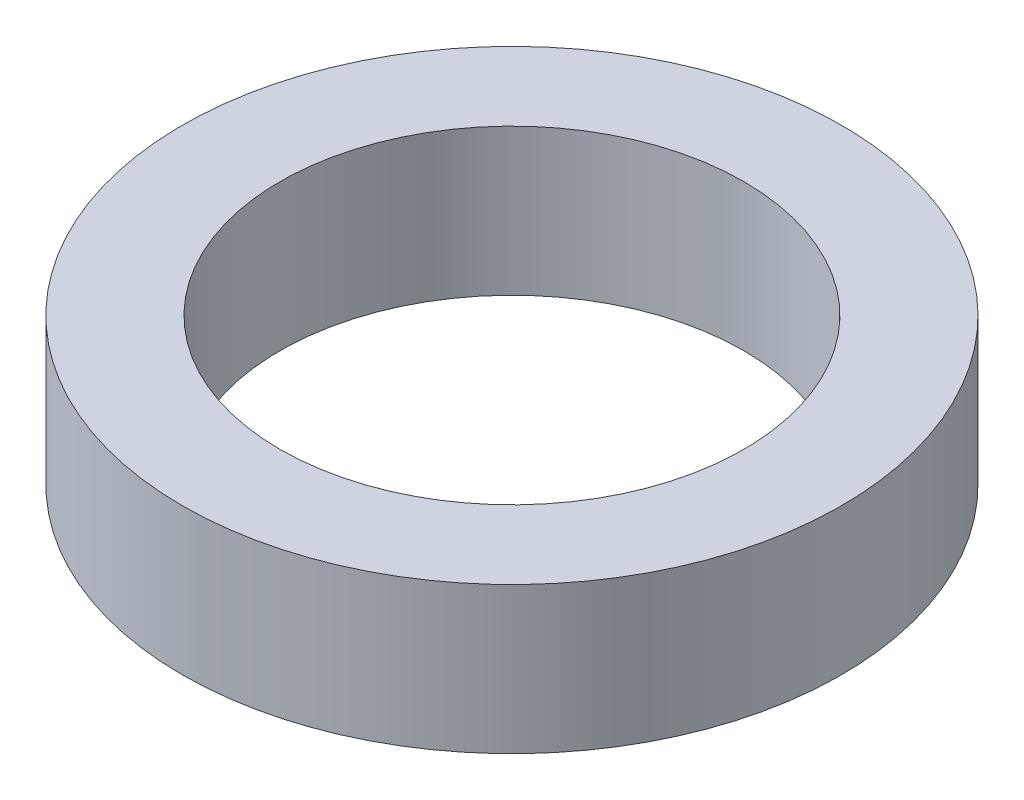
SolidWorks part; units mm, degrees
ref_plane "Front Plane" through (0, 0, 0) normal (0, 0, 1) x (1, 0, 0)
ref_plane "Top Plane" through (0, 0, 0) normal (0, 1, 0) x (1, 0, 0)
ref_plane "Right Plane" through (0, 0, 0) normal (1, 0, 0) x (0, 0, -1)
sketch "Sketch1" plane through (0, 0, 0) normal (0, 1, 0) x (1, 0, 0)
  circle A0 centre (0, 0) radius 67.5
  dimension "FLANGE_OD" = 135
extrude "Boss-Extrude1" add sketch "Sketch1" along normal blind 30
sketch "Sketch2" plane through (0, 0, 0) normal (0, 1, 0) x (1, 0, 0)
  circle A0 centre (0, 0) radius 47.5
  dimension "BORE_D" = 95
extrude "Cut-Extrude1" cut sketch "Sketch2" along normal through all
sketch "Sketch3" plane through (0, 30, 0) normal (0, 1, 0) x (1, 0, 0)
  circle A0 centre (0, 0) radius 30.3804 construction
  circle A1 centre (-30.3804, 0) radius 2.7107
  dimension "BOLT_D" = 5.4215
  dimension "BOLT_PCD" = 60.7609
extrude "Cut-Extrude2" cut sketch "Sketch3" against normal blind 20.9159 rebuild error yes
pattern_circular "CirPattern1" count 4 over 360 rebuild error yes
